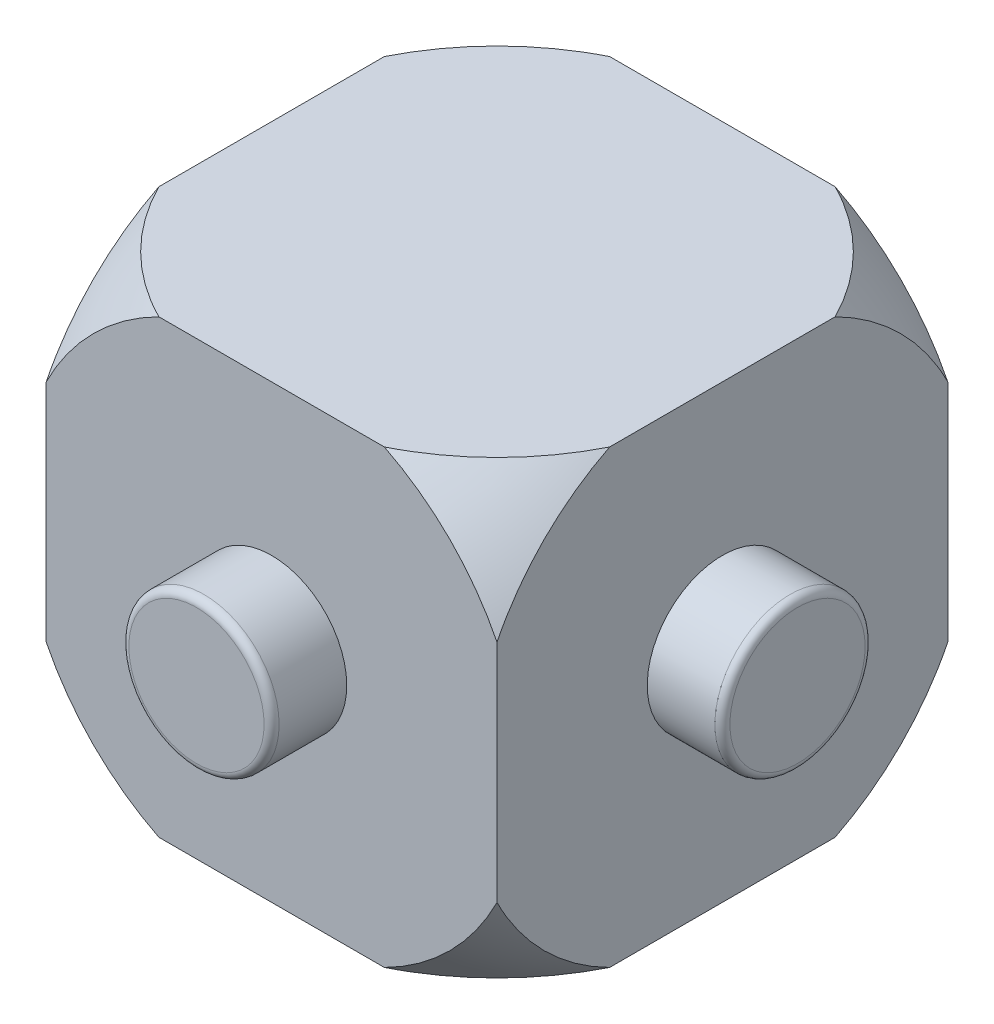
SolidWorks part; units mm, degrees
material "不锈钢 (铁素体)"
ref_plane "前视基准面" through (0, 0, 0) normal (0, 0, 1) x (1, 0, 0)
ref_plane "上视基准面" through (0, 0, 0) normal (0, 1, 0) x (1, 0, 0)
ref_plane "右视基准面" through (0, 0, 0) normal (1, 0, 0) x (0, 0, -1)
sketch "草图1" plane through (0, 0, 0) normal (0, 0, 1) x (1, 0, 0)
  line L1 (-3, 3) -> (3, 3)
  line L2 (-3, 3) -> (-3, -3)
  line L3 (-3, -3) -> (3, -3)
  line L4 (3, 3) -> (3, -3)
  line L5 (-3, 3) -> (3, -3) construction
  line L6 (-3, -3) -> (3, 3) construction
  point P0 (0, 0)
  dimension "D1" = 6
  dimension "D2" = 6
extrude "凸台-拉伸1" add sketch "草图1" along normal mid plane 6
sketch "草图4" plane through (0, 0, 0) normal (0, 1, 0) x (1, 0, 0)
  line L0 (0, 4.5) -> (0, -4.5) construction
  line L1 (0, 4.5) -> (0, -4.5) construction
  line L2 (0, -4.5) -> (0, -6.3186)
  line L3 (-7, 6.2888) -> (-7, -6.3186)
  line L4 (0, -6.3186) -> (-7, -6.3186)
  line L5 (0, 4.5) -> (0, 6.2888)
  line L6 (0, 6.2888) -> (-7, 6.2888)
  arc A0 (0, 4.5) -> (0, -4.5) centre (0, 0) ccw
  dimension "D1" = 4.5
  dimension "D2" = 7
revolve "切除-旋转4" cut sketch "草图4" angle 360 about L0
sketch "草图2" plane through (0, 0, 0) normal (0, 0, 1) x (1, 0, 0)
  circle A0 centre (0, 0) radius 1
extrude "凸台-拉伸2" add sketch "草图2" along normal mid plane 8
sketch "草图3" plane through (0, 0, 0) normal (1, 0, 0) x (0, 0, -1)
  circle A0 centre (0, 0) radius 1
extrude "凸台-拉伸3" add sketch "草图3" along normal mid plane 8
fillet "圆角1" radius 0.1 4 edges at (4, 0, -1) (1, 0, -4) (-4, 0, -1) (1, 0, 4)
ref_axis "基准轴1" through (0, 0, -3.3) along (0, 0, 1)
